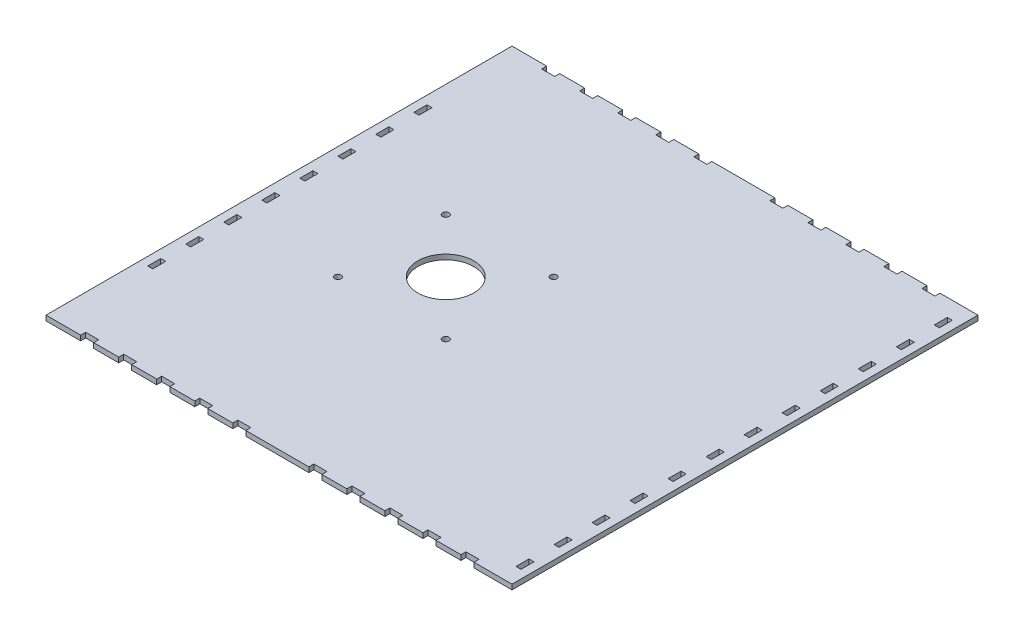
SolidWorks part; units mm, degrees
material "ENPH 253 Hardboard"
ref_plane "Front Plane" through (0, 0, 0) normal (0, 0, 1) x (1, 0, 0)
ref_plane "Top Plane" through (0, 0, 0) normal (0, 1, 0) x (1, 0, 0)
ref_plane "Right Plane" through (0, 0, 0) normal (1, 0, 0) x (0, 0, -1)
sketch "Sketch1" plane through (0, 0, 0) normal (0, 1, 0) x (1, 0, 0)
  line L0 (0, -139.7) -> (0, 139.7) construction
  line L1 (-139.7, 139.7) -> (139.7, 139.7)
  line L2 (-139.7, 139.7) -> (-139.7, -139.7)
  line L3 (-139.7, -139.7) -> (139.7, -139.7)
  line L4 (139.7, 139.7) -> (139.7, -139.7)
  line L5 (-139.7, 139.7) -> (139.7, -139.7) construction
  line L6 (-139.7, -139.7) -> (139.7, 139.7) construction
  line L12 (-139.7, 0) -> (139.7, 0) construction
  point P0 (0, 0)
  dimension "D1" = 279.4
  dimension "D2" = 279.4
extrude "Boss-Extrude1" add sketch "Sketch1" along normal blind 3
sketch "Sketch3" plane through (0, 0, 0) normal (0, -1, 0) x (-1, 0, 0)
  line L0 (-139.7, -139.7) -> (-139.7, 139.7) construction
  line L1 (-134.7, 129.3) -> (-131.7, 129.3)
  line L2 (-134.7, 129.3) -> (-134.7, 121.5)
  line L3 (-134.7, 121.5) -> (-131.7, 121.5)
  line L4 (-131.7, 129.3) -> (-131.7, 121.5)
  line L5 (-139.7, 139.7) -> (139.7, 139.7) construction
  dimension "D1" = 5
  dimension "D2" = 10.4
  dimension "D3" = 7.8
  dimension "D4" = 3
extrude "Cut-Extrude2" cut sketch "Sketch3" against normal through all
pattern_linear "LPattern1" count 12 spacing 22.8 along (0, 0, 1) of "Cut-Extrude2"
sketch "Sketch5" plane through (0, 0, 0) normal (0, -1, 0) x (1, 0, 0)
  line L0 (139.7, -139.7) -> (-139.7, -139.7) construction
  line L1 (109.1, -139.7) -> (116.9, -139.7)
  line L2 (109.1, -139.7) -> (109.1, -136.7)
  line L3 (109.1, -136.7) -> (116.9, -136.7)
  line L4 (116.9, -139.7) -> (116.9, -136.7)
  line L5 (139.7, 139.7) -> (139.7, -139.7) construction
  dimension "D1" = 22.8
  dimension "D2" = 7.8
  dimension "D3" = 3
extrude "Cut-Extrude3" cut sketch "Sketch5" against normal through all
pattern_linear "LPattern2" count 11 spacing 22.8 along (-1, 0, 0) skipping (5, 0) of "Cut-Extrude3"
mirror "Mirror2" about plane through (0, 0, 0) normal (0, 0, 1) of "LPattern2"
sketch "Sketch6" plane through (0, 0, 0) normal (0, -1, 0) x (1, 0, 0)
  line L0 (63.5, -139.7) -> (48.5, -139.7) construction
  line L1 (-134.7, -83.7) -> (-131.7, -83.7)
  line L2 (-134.7, -83.7) -> (-134.7, -75.9)
  line L3 (-134.7, -75.9) -> (-131.7, -75.9)
  line L4 (-131.7, -83.7) -> (-131.7, -75.9)
  line L5 (-139.7, -139.7) -> (-139.7, 139.7) construction
  dimension "D1" = 56
  dimension "D2" = 5
  dimension "D3" = 3
  dimension "D4" = 7.8
extrude "Cut-Extrude4" cut sketch "Sketch6" against normal through all
pattern_linear "LPattern3" count 8 spacing 22.8 along (0, 0, 1) of "Cut-Extrude4"
sketch "Sketch7" plane through (0, 0, 0) normal (0, -1, 0) x (-1, 0, 0)
  line L0 (7.375, 32.325) -> (7.375, -32.325) construction
  line L1 (139.7, 139.7) -> (139.7, -139.7) construction
  line L3 (-63.5, 139.7) -> (-48.5, 139.7) construction
  line L5 (72.025, 32.325) -> (7.375, 32.325) construction
  line L7 (7.375, -32.325) -> (72.025, -32.325) construction
  line L8 (72.025, -32.325) -> (72.025, 32.325) construction
  circle A0 centre (39.7, 0) radius 16.75
  circle A1 centre (72.025, -32.325) radius 1.95
  circle A2 centre (7.375, -32.325) radius 1.95
  circle A3 centre (72.025, 32.325) radius 1.95
  circle A4 centre (7.375, 32.325) radius 1.95
  dimension "D1" = 33.5
  dimension "D8" = 3.9
  dimension "D9" = 3.9
  dimension "D10" = 3.9
  dimension "D11" = 3.9
  dimension "D2" = 100
  dimension "D3" = 139.7
  dimension "D4" = 64.65
  dimension "D5" = 64.65
  dimension "D6" = 32.325
  dimension "D7" = 32.325
extrude "Cut-Extrude5" cut sketch "Sketch7" against normal through all
